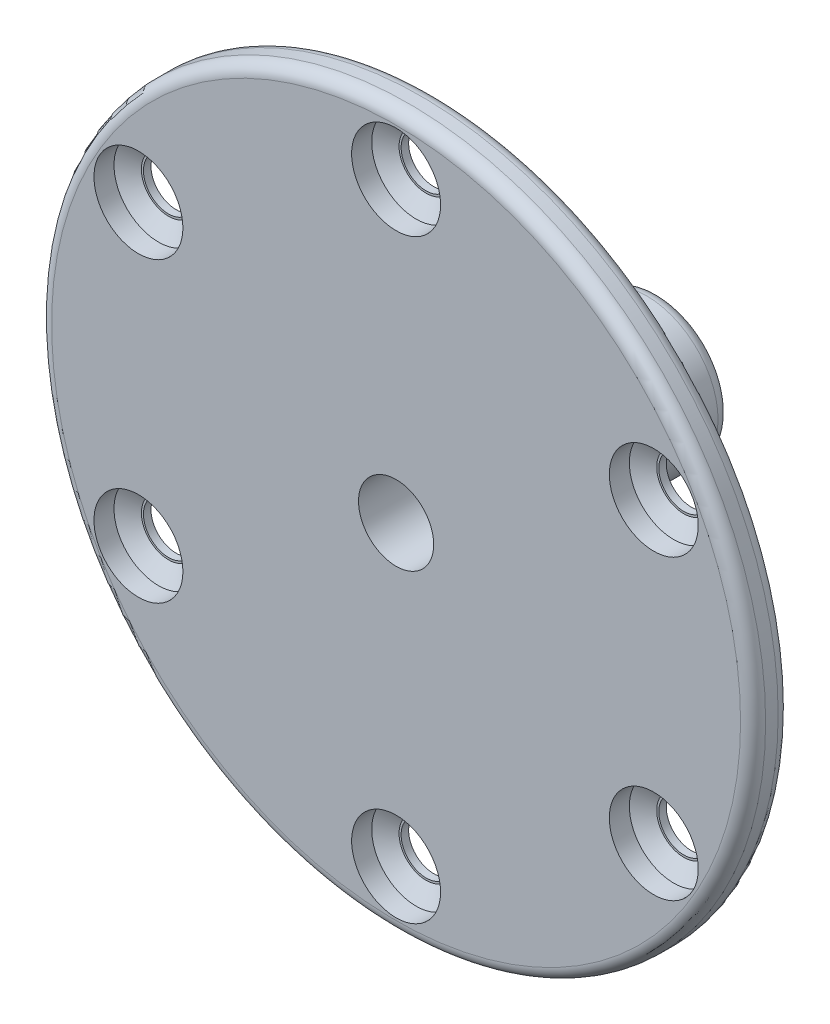
SolidWorks part; units mm, degrees
ref_plane "Front Plane" through (0, 0, 0) normal (1, 0, 0) x (0, 1, 0)
ref_plane "Top Plane" through (0, 0, 0) normal (0, 0, 1) x (0, 1, 0)
ref_plane "Right Plane" through (0, 0, 0) normal (0, 1, 0) x (-1, 0, 0)
sketch "Sketch1" plane through (0, 0, 0) normal (0, 0, 1) x (0, 1, 0)
  circle A3 centre (-23.75, 0) radius 2
  circle A4 centre (0, 0) radius 23.75 construction
  circle A5 centre (-11.875, 20.5681) radius 2
  circle A6 centre (11.875, 20.5681) radius 2
  circle A7 centre (23.75, 0) radius 2
  circle A8 centre (11.875, -20.5681) radius 2
  circle A9 centre (-11.875, -20.5681) radius 2
  circle A10 centre (0, 0) radius 28.5
  circle A11 centre (0, 0) radius 5.7
  circle A12 centre (0, 0) radius 3
  dimension "D1" = 47.5
  dimension "D2" = 6
  dimension "D3" = 4
  dimension "D4" = 57
  dimension "D5" = 11.4
  dimension "D6" = 6
extrude "Boss-Extrude1" add sketch "Sketch1" along normal blind 3 contours A10 A11 A3 A5 A6 A7 A8 A9 | A11 A12 region at (0, -27.6939, 0) region at (0, -5.5388, 0)
sketch "Sketch2" plane through (0, 0, 3) normal (0, 0, 1) x (1, 0, 0)
  circle A2 centre (-20.5681, -11.875) radius 3.55
  circle A3 centre (-20.5681, 11.875) radius 3.55
  circle A4 centre (0, 23.75) radius 3.55
  circle A5 centre (20.5681, 11.875) radius 3.55
  circle A6 centre (20.5681, -11.875) radius 3.55
  circle A7 centre (0, -23.75) radius 3.55
  point P2 (18.4681, -1.0482)
  point P4 (-58.8298, -20.265)
  point P5 (-20.5681, 11.875)
  dimension "D1" = 7.1
  dimension "D2" = 6
extrude "Cut-Extrude1" cut sketch "Sketch2" against normal blind 2.4
extrude "Boss-Extrude2" add sketch "Sketch1<4>" against normal blind 12 contours A11 A12 region at (0, -5.5388, 0)
sketch "Sketch1<4>" plane through (0, 0, 0) normal (0, 0, 1) x (0, 1, 0) same geometry as "Sketch1"
sketch "Sketch3" plane through (0, 0, 0) normal (0, 1, 0) x (-1, 0, 0)
  line L0 (0, 3) -> (0, -12) construction
  line L1 (-5.7, -12) -> (5.7, -12) construction
  circle A0 centre (0, -4) radius 1.5
  dimension "D1" = 3
  dimension "D2" = 8
sketch "Sketch4" plane through (0, 0, -12) normal (0, 0, -1) x (1, 0, 0)
  circle A0 centre (0, 0) radius 2
  circle A1 centre (0, 0) radius 5.7 construction
  circle A2 centre (0, 0) radius 5.7
  dimension "D1" = 4
extrude "Boss-Extrude3" add sketch "Sketch4" along normal blind 6
extrude "Cut-Extrude2" cut sketch "Sketch3" against normal up to next and the other way up to next
fillet "Fillet1" radius 1 4 edges at (28.5, 0, 3) (28.5, 0, 0) (-5.7, 0, -18) (5.7, 0, 0)
chamfer "Chamfer1" distance 1.4 angle 45 1 edges at (-2, 0, -12)
chamfer "Chamfer2" distance 0.8 angle 60 6 edges at (24.1181, -11.875, 0.6) (24.1181, 11.875, 0.6) (3.55, 23.75, 0.6) (3.55, -23.75, 0.6) (-17.0181, -11.875, 0.6) (-17.0181, 11.875, 0.6) first distance on face at (24.1181, -11.875, 0.6) first distance on face at (24.1181, 11.875, 0.6) first distance on face at (3.55, 23.75, 0.6) first distance on face at (3.55, -23.75, 0.6) first distance on face at (-17.0181, -11.875, 0.6) first distance on face at (-17.0181, 11.875, 0.6)
